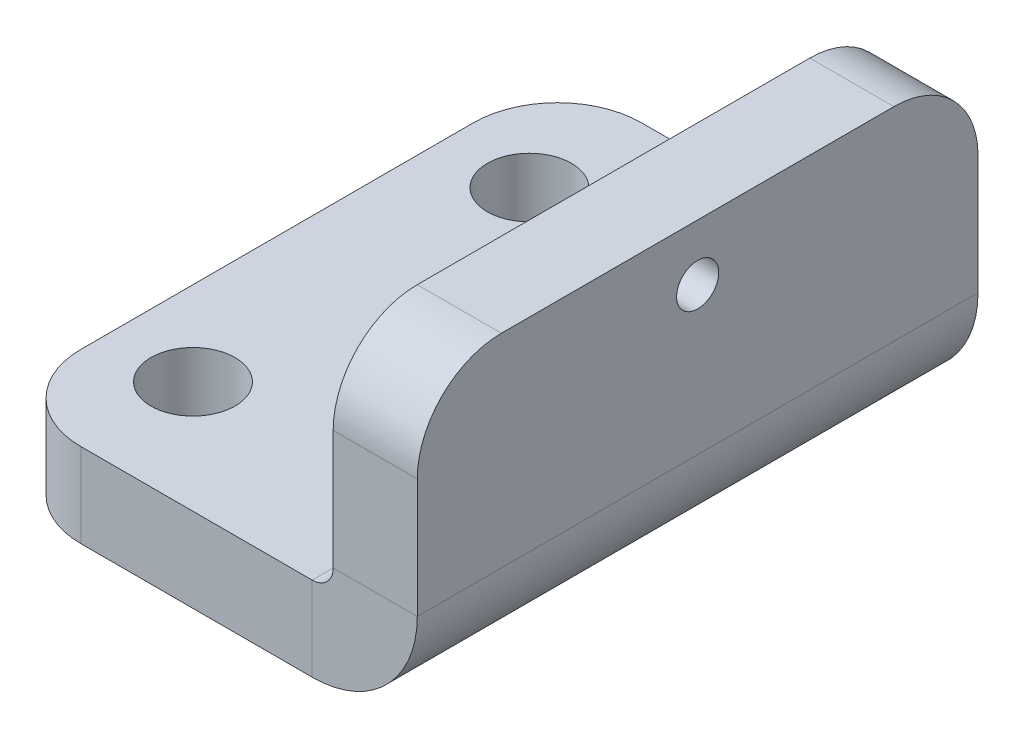
SolidWorks part; units mm, degrees
note: The reader was unsure of these and kept them because the rebuilt part matched: thickness of "Base-Flange1", "Sheet-Metal1", "Sheet-Metal2", "Sheet-Metal3"; bend radius of "BaseBend1".
ref_plane "Front Plane" through (0, 0, 0) normal (0, 0, 1) x (1, 0, 0)
ref_plane "Top Plane" through (0, 0, 0) normal (0, 1, 0) x (1, 0, 0)
ref_plane "Right Plane" through (0, 0, 0) normal (1, 0, 0) x (0, 0, -1)
sketch "Sketch1" plane through (0, 0, 0) normal (0, 0, 1) x (1, 0, 0)
  line L0 (-12, 0) -> (0, 0)
  line L1 (0, 0) -> (0, 8)
  dimension "D1" = 8
  dimension "D2" = 12
base flange "Base-Flange1" sketch "Sketch1" end condition mid plane depth 20 reverse direction no thickness 3 reverse thickness direction no bend radius 0.75
bend "BaseBend1" bend radius 0.75 bend angle 90 parameters "D5"=1
fillet "Fillet1" radius 3 4 edges at (-12, -1.5, -10) (-12, -1.5, 10) (1.5, 8, 10) (1.5, 8, -10)
sketch "Sketch6" plane through (0, 0, 0) normal (0, 1, 0) x (1, 0, 0)
  line L0 (-12, -7) -> (-12, 7) construction
  line L1 (0, 0) -> (-12, 0) construction
  circle A0 centre (-9, 6) radius 1.5
  circle A1 centre (-9, -6) radius 1.5
  dimension "D2" = 3
  dimension "D1" = 3
  dimension "D3" = 6
extrude "Cut-Extrude1" cut sketch "Sketch6" against normal through all normal cut yes
sketch "Sketch7" plane through (0, 0, 0) normal (-1, 0, 0) x (0, 0, 1)
  line L0 (0, 0) -> (0, 8) construction
  line L1 (7, 8) -> (-7, 8) construction
  circle A0 centre (0, 6) radius 0.75
  dimension "D1" = 1.5
  dimension "D2" = 2
extrude "Cut-Extrude2" cut sketch "Sketch7" against normal through all normal cut yes
sketch "Bend-Lines1" [suppressed] plane through (0, 0, 0) normal (0, 1, 0) x (1, 0, 0)
sketch "Bounding-Box1" [suppressed] plane through (0, 0, 0) normal (0, 1, 0) x (1, 0, 0)
sheet metal parameters "Sheet-Metal1" thickness 3 parameters "D1"=0.75
flat pattern "Flat-Pattern1" [suppressed]
sketch "Bend-Lines2" plane through (0, 0, 0) normal (0, 1, 0) x (1, 0, 0)
  line L0 (0.6244, 10) -> (0.6244, -10) construction
  line L1 (0.6244, 10) -> (0.6244, -10) construction
sketch3d "Bounding-Box2" [suppressed]
  line L0 (0, 0, 0) -> (21.2489, 0, 0) construction
  line L1 (0, 20, 0) -> (21.2489, 20, 0) construction
  line L2 (0, 0, 0) -> (0, 20, 0) construction
  line L3 (21.2489, 0, 0) -> (21.2489, 20, 0) construction
bend of the flat pattern "Flatten-<BaseBend1>1"
sheet metal parameters "Sheet-Metal2" thickness 3 parameters "D1"=0.75, "D7"=2
flat pattern "Flat-Pattern1"
sketch "Bend-Lines2" plane through (0, 0, 0) normal (0, 1, 0) x (1, 0, 0)
  line L0 (0.6244, 10) -> (0.6244, -10) construction
  line L1 (0.6244, 10) -> (0.6244, -10) construction
sketch3d "Bounding-Box2" [suppressed]
  line L0 (0, 0, 0) -> (21.2489, 0, 0) construction
  line L1 (0, 20, 0) -> (21.2489, 20, 0) construction
  line L2 (0, 0, 0) -> (0, 20, 0) construction
  line L3 (21.2489, 0, 0) -> (21.2489, 20, 0) construction
bend of the flat pattern "Flatten-<BaseBend1>1"
sheet metal parameters "Sheet-Metal3" thickness 3 parameters "D1"=0.75, "D7"=2
flat pattern "Flat-Pattern1"
sketch "Bend-Lines2" plane through (0, 0, 0) normal (0, 1, 0) x (1, 0, 0)
  line L0 (1.0171, 10) -> (1.0171, -10) construction
  line L1 (1.0171, 10) -> (1.0171, -10) construction
sketch3d "Bounding-Box2" [suppressed]
  line L0 (0, 0, 0) -> (22.0343, 0, 0) construction
  line L1 (0, 20, 0) -> (22.0343, 20, 0) construction
  line L2 (0, 0, 0) -> (0, 20, 0) construction
  line L3 (22.0343, 0, 0) -> (22.0343, 20, 0) construction
bend of the flat pattern "Flatten-<BaseBend1>1"
